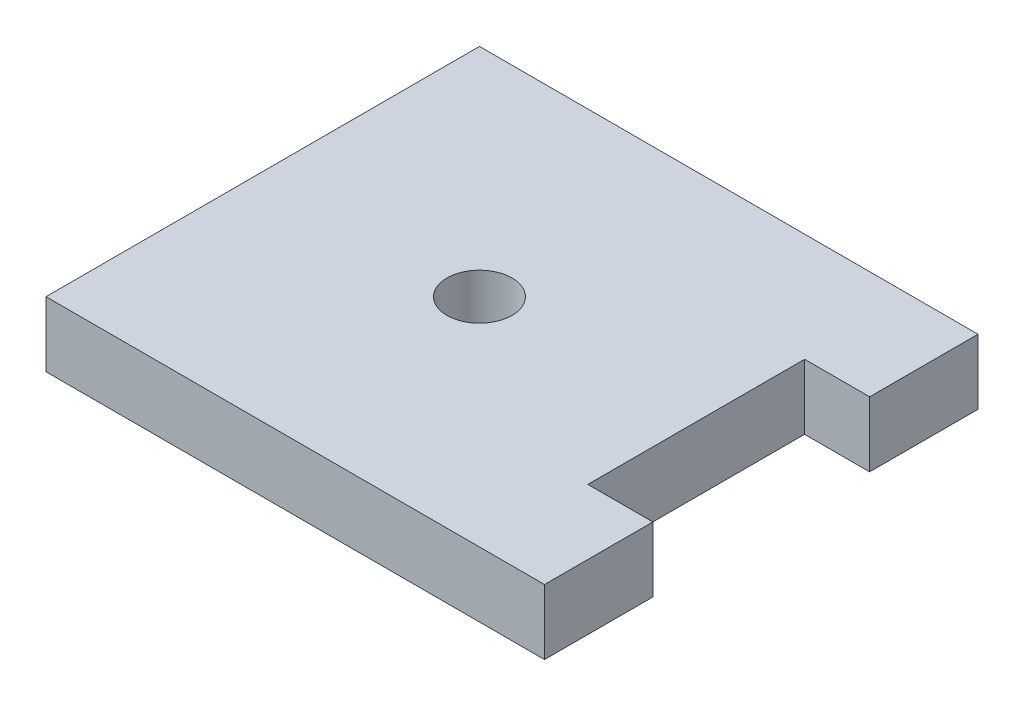
SolidWorks part; units mm, degrees
ref_plane "Front Plane" through (0, 0, 0) normal (0, 0, 1) x (1, 0, 0)
ref_plane "Top Plane" through (0, 0, 0) normal (0, 1, 0) x (1, 0, 0)
ref_plane "Right Plane" through (0, 0, 0) normal (1, 0, 0) x (0, 0, -1)
sketch "Sketch1" plane through (0, 0, 0) normal (0, 1, 0) x (1, 0, 0)
  line L0 (10, 20) -> (10, 0) construction
  line L1 (0, 0) -> (20, 0)
  line L2 (0, 0) -> (0, 20)
  line L3 (0, 20) -> (20, 20)
  line L4 (20, 5) -> (20, 15)
  line L9 (0, 10) -> (20, 10) construction
  line L10 (20, 5) -> (23, 5)
  line L11 (20, 20) -> (23, 20)
  line L13 (20, 15) -> (23, 15)
  line L14 (23, 20) -> (23, 15)
  line L15 (23, 0) -> (23, 5)
  line L16 (20, 0) -> (23, 0)
  circle A0 centre (10, 10) radius 1.5
  dimension "D1" = 20
  dimension "D2" = 20
  dimension "D3" = 3
  dimension "D4" = 5
extrude "Boss-Extrude1" add sketch "Sketch1" along normal blind 3
